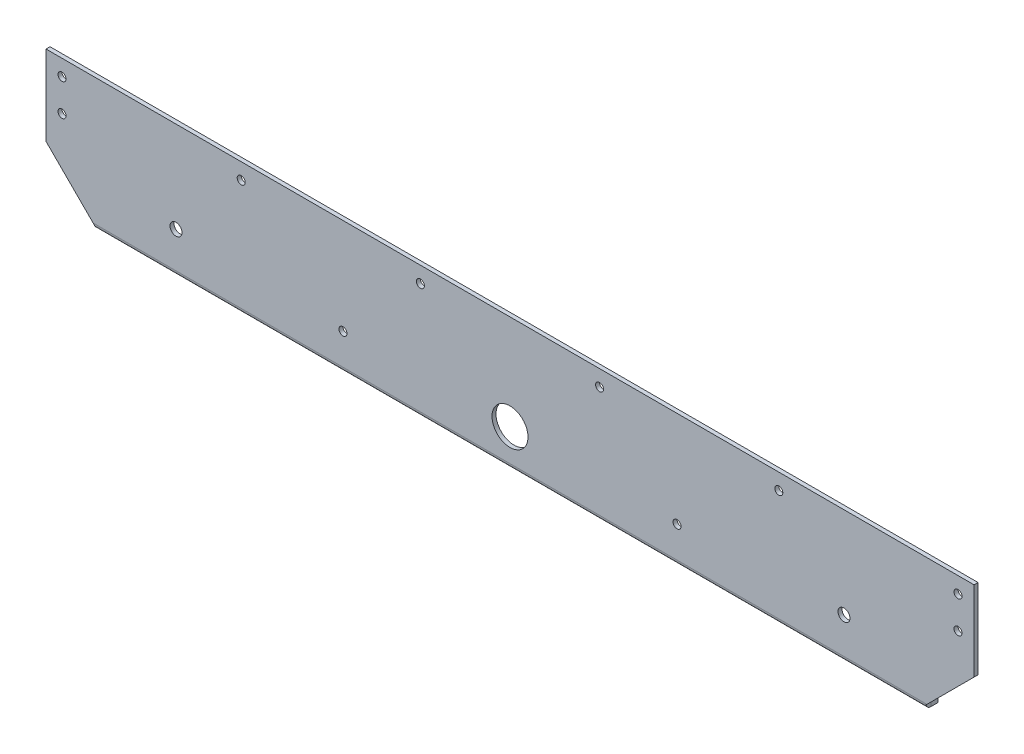
SolidWorks part; units mm, degrees
note: The reader was unsure of these and kept them because the rebuilt part matched: flange length of "Edge-Flange1".
ref_plane "Front Plane" through (0, 0, 0) normal (0, 0, 1) x (1, 0, 0)
ref_plane "Top Plane" through (0, 0, 0) normal (0, 1, 0) x (1, 0, 0)
ref_plane "Right Plane" through (0, 0, 0) normal (1, 0, 0) x (0, 0, -1)
sketch "Sketch1" plane through (0, 0, 0) normal (0, 0, 1) x (1, 0, 0)
  line L1 (-368.3, 50.8) -> (368.3, 50.8)
  line L2 (-368.3, 50.8) -> (-368.3, -50.8)
  line L3 (-368.3, -50.8) -> (368.3, -50.8)
  line L4 (368.3, 50.8) -> (368.3, -50.8)
  line L5 (-368.3, 50.8) -> (368.3, -50.8) construction
  line L6 (-368.3, -50.8) -> (368.3, 50.8) construction
  point P0 (0, 0)
  dimension "D1" = 736.6
  dimension "D2" = 101.6
base flange "Base-Flange1" sketch "Sketch1" thickness 3.175 reverse thickness direction no parameters "D1"=0.7366
sketch "Sketch11" plane through (0, 0, 0) normal (0, 0, 1) x (1, 0, 0)
  line L0 (-368.3, -50.8) -> (-330.2, -50.8)
  line L1 (-368.3, -50.8) -> (368.3, -50.8) construction
  line L2 (-330.2, -50.8) -> (-368.3, -12.7)
  line L3 (-368.3, 50.8) -> (-368.3, -50.8) construction
  line L4 (-368.3, -12.7) -> (-368.3, -50.8)
  line L5 (368.3, -50.8) -> (330.2, -50.8)
  line L6 (330.2, -50.8) -> (368.3, -12.7)
  line L7 (368.3, -50.8) -> (368.3, 50.8) construction
  line L8 (368.3, -12.7) -> (368.3, -50.8)
  dimension "D1" = 38.1
  dimension "D2" = 38.1
extrude "Cut-Extrude2" cut sketch "Sketch11" against normal blind 3.175 normal cut yes
edge flange "Edge-Flange1" sketch "Sketch8" flange angle 90 flange length 6.35 flange position material outside bend radius 0.7366 thickness 3.175 relief none parameters "D6"=10
sketch "Sketch8" plane through (0, -50.8, -3.175) normal (0, -1, 0) x (-1, 0, 0)
  line L2 (-330.2, 0) -> (-330.2, 6.35)
  line L3 (-330.2, 6.35) -> (330.2, 6.35)
  line L4 (330.2, 6.35) -> (330.2, 0)
  line L5 (330.2, 0) -> (-330.2, 0) construction
  line L6 (330.2, 0) -> (-330.2, 0)
bend "EdgeBend1" bend radius 0.7366 bend angle 90 parameters "D5"=1
sketch "Sketch12" plane through (0, 0, 0) normal (0, 0, 1) x (1, 0, 0)
  line L0 (-368.3, -12.7) -> (0, -24.6634) construction
  line L1 (0, -24.6634) -> (368.3, -12.7) construction
  line L2 (-330.2, -50.0634) -> (330.2, -50.0634) construction
  line L3 (0, -24.6634) -> (-265.1125, -21.4884) construction
  line L4 (0, -24.6634) -> (265.1125, -21.4884) construction
  circle A0 centre (0, -24.6634) radius 14.2875
  circle A1 centre (-265.1125, -21.4884) radius 4.7625
  circle A2 centre (265.1125, -21.4884) radius 4.7625
  dimension "D2" = 28.575
  dimension "D4" = 9.525
  dimension "D1" = 25.4
  dimension "D3" = 3.175
  dimension "D5" = 265.1125
extrude "Cut-Extrude3" cut sketch "Sketch12" against normal through all normal cut yes
sketch "Sketch13" plane through (0, 0, 0) normal (0, 0, 1) x (1, 0, 0)
  line L0 (368.3, -12.7) -> (368.3, 50.8) construction
  line L1 (368.3, 50.8) -> (-368.3, 50.8) construction
  line L2 (0, 50.8) -> (0, 0) construction
  line L3 (-355.6, 38.1) -> (-213.36, 38.1) construction
  line L4 (-265.1125, -21.4884) -> (-132.5841, -25.4) construction
  line L5 (-213.36, 38.1) -> (-71.12, 38.1) construction
  line L6 (-71.12, 38.1) -> (71.12, 38.1) construction
  line L8 (71.12, 38.1) -> (213.36, 38.1) construction
  line L9 (213.36, 38.1) -> (355.6, 38.1) construction
  line L10 (-132.5841, -25.4) -> (0, -24.6634) construction
  line L11 (0, -24.6634) -> (132.5841, -25.4) construction
  line L12 (132.5841, -25.4) -> (265.1125, -21.4884) construction
  circle A0 centre (355.6, 38.1) radius 3.175
  circle A1 centre (355.6, 12.7) radius 3.175
  circle A2 centre (-355.6, 12.7) radius 3.175
  circle A3 centre (-355.6, 38.1) radius 3.175
  circle A4 centre (-213.36, 38.1) radius 3.175
  circle A5 centre (-71.12, 38.1) radius 3.175
  circle A7 centre (71.12, 38.1) radius 3.175
  circle A8 centre (213.36, 38.1) radius 3.175
  circle A9 centre (-132.5841, -25.4) radius 3.175
  circle A10 centre (132.5841, -25.4) radius 3.175
  dimension "D2" = 6.35
  dimension "D1" = 12.7
  dimension "D3" = 25.4
  dimension "D4" = 12.7
  dimension "D5" = 63.5
extrude "Cut-Extrude4" cut sketch "Sketch13" against normal through all normal cut yes
sketch "Sketch14" plane through (0, 0, 0) normal (0, 0, 1) x (1, 0, 0)
  line L0 (0, -24.6634) -> (-36.195, 45.2645) construction
  line L1 (0, -24.6634) -> (36.195, 45.2645) construction
  line L3 (-36.576, -41.0955) -> (0, -24.6634) construction
  line L4 (0, -24.6634) -> (36.576, -41.0955) construction
  circle A0 centre (-36.195, 45.2645) radius 1.905
  circle A1 centre (36.195, 45.2645) radius 1.905
  circle A2 centre (-36.576, -41.0955) radius 1.905
  circle A3 centre (36.576, -41.0955) radius 1.905
  point P8 (21.7003, -37.9372)
  point P9 (83.7969, -44.4705)
  point P10 (46.5941, -41.0955)
  point P13 (71.8287, -68.6002)
  point P14 (29.8265, -41.0955)
  dimension "D3" = 3.81
  dimension "D1" = 72.39
  dimension "D2" = 78.74
  dimension "D4" = 86.36
  dimension "D5" = 36.576
sketch "Bend-Lines1" [suppressed] plane through (0, 0, 0) normal (0, 1, 0) x (1, 0, 0)
sketch "Bounding-Box1" [suppressed] plane through (0, 0, 0) normal (0, 1, 0) x (1, 0, 0)
sheet metal parameters "Sheet-Metal1" thickness 3.175 parameters "D1"=0.7366
flat pattern "Flat-Pattern1" [suppressed]
sketch "Bend-Lines2" plane through (0, 0, 0) normal (0, 1, 0) x (1, 0, 0)
sketch3d "Bounding-Box2" [suppressed]
  line L0 (-368.3, -50.8, 0) -> (368.3, -50.8, 0) construction
  line L1 (-368.3, 50.8, 0) -> (368.3, 50.8, 0) construction
  line L2 (-368.3, -50.8, 0) -> (-368.3, 50.8, 0) construction
  line L3 (368.3, -50.8, 0) -> (368.3, 50.8, 0) construction
sheet metal parameters "Sheet-Metal2" thickness 3.175 parameters "D1"=0.7366
flat pattern "Flat-Pattern1"
sketch "Bend-Lines2" plane through (0, 0, 0) normal (0, 0, 1) x (1, 0, 0)
  line L0 (-368.3, -48.7137) -> (368.3, -48.7137) construction
  line L1 (-368.3, -48.7137) -> (368.3, -48.7137) construction
sketch3d "Bounding-Box2" [suppressed]
  line L0 (-368.3, -56.1525, 0) -> (368.3, -56.1525, 0) construction
  line L1 (-368.3, 50.8, 0) -> (368.3, 50.8, 0) construction
  line L2 (-368.3, -56.1525, 0) -> (-368.3, 50.8, 0) construction
  line L3 (368.3, -56.1525, 0) -> (368.3, 50.8, 0) construction
bend of the flat pattern "Flatten-<EdgeBend1>1"
sheet metal parameters "Sheet-Metal4" thickness 3.175 parameters "D1"=0.7366
flat pattern "Flat-Pattern1"
sketch "Bend-Lines2" plane through (0, 0, 0) normal (0, 1, 0) x (1, 0, 0)
sketch3d "Bounding-Box2" [suppressed]
  line L0 (-368.3, -50.8, 0) -> (368.3, -50.8, 0) construction
  line L1 (-368.3, 50.8, 0) -> (368.3, 50.8, 0) construction
  line L2 (-368.3, -50.8, 0) -> (-368.3, 50.8, 0) construction
  line L3 (368.3, -50.8, 0) -> (368.3, 50.8, 0) construction
sheet metal parameters "Sheet-Metal5" thickness 3.175 parameters "D1"=0.7366
flat pattern "Flat-Pattern1"
sketch "Bend-Lines2" plane through (0, 0, 0) normal (0, 0, 1) x (1, 0, 0)
  line L0 (-368.3, -48.7137) -> (368.3, -48.7137) construction
  line L1 (-368.3, -48.7137) -> (368.3, -48.7137) construction
sketch3d "Bounding-Box2" [suppressed]
  line L0 (-368.3, -56.1525, 0) -> (368.3, -56.1525, 0) construction
  line L1 (-368.3, 50.8, 0) -> (368.3, 50.8, 0) construction
  line L2 (-368.3, -56.1525, 0) -> (-368.3, 50.8, 0) construction
  line L3 (368.3, -56.1525, 0) -> (368.3, 50.8, 0) construction
bend of the flat pattern "Flatten-<EdgeBend1>1"
sheet metal parameters "Sheet-Metal6" thickness 3.175 parameters "D1"=0.7366
flat pattern "Flat-Pattern1"
sketch "Bend-Lines2" plane through (0, 0, 0) normal (0, 0, 1) x (1, 0, 0)
  line L0 (-368.3, -48.7137) -> (368.3, -48.7137) construction
  line L1 (-368.3, -48.7137) -> (368.3, -48.7137) construction
sketch3d "Bounding-Box2" [suppressed]
  line L0 (-368.3, -56.1525, 0) -> (368.3, -56.1525, 0) construction
  line L1 (-368.3, 50.8, 0) -> (368.3, 50.8, 0) construction
  line L2 (-368.3, -56.1525, 0) -> (-368.3, 50.8, 0) construction
  line L3 (368.3, -56.1525, 0) -> (368.3, 50.8, 0) construction
bend of the flat pattern "Flatten-<EdgeBend1>1"
